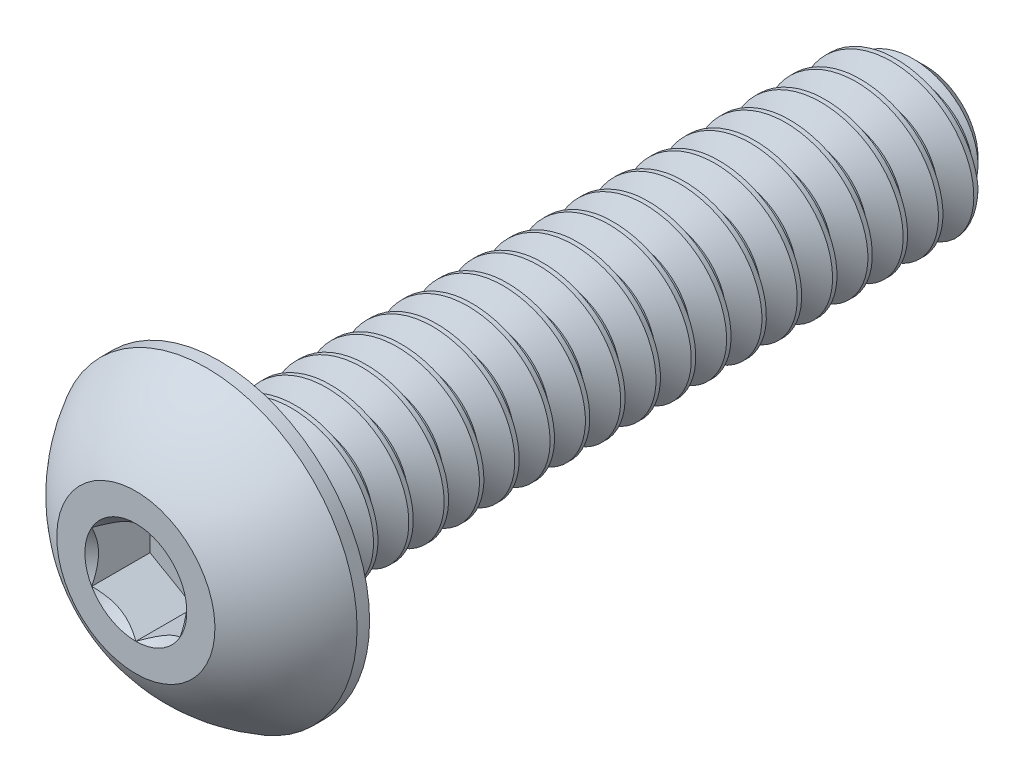
SolidWorks part; units mm, degrees
ref_plane "Front" through (0, 0, 0) normal (0, 0, 1) x (1, 0, 0)
ref_plane "Top" through (0, 0, 0) normal (0, 1, 0) x (1, 0, 0)
ref_plane "Right" through (0, 0, 0) normal (1, 0, 0) x (0, 0, -1)
sketch "Sketch1" plane through (0, 0, 0) normal (1, 0, 0) x (0, 0, -1)
  line L2 (1.4986, 1.4224) -> (14.1986, 1.4224)
  line L3 (14.1986, 1.4224) -> (14.1986, 0)
  line L4 (14.1986, 0) -> (1.4986, 0)
  line L6 (1.2738, 2.7051) -> (1.4986, 2.7051) construction
  line L7 (14.1986, 1.4224) -> (14.1986, -1.4224) construction
  line L8 (0, 0) -> (1.4986, 0) construction
  line L9 (1.4986, 2.7051) -> (1.4986, -2.7051) construction
  line L11 (1.4986, 1.4224) -> (1.4986, 0)
  line L13 (0, 0.7937) -> (0, -0.7937) construction
  line L14 (0, 0.7937) -> (0, 1.4224) construction
  arc A3 (0, 1.4224) -> (1.2738, 2.7051) centre (2.7151, 0) cw construction
  dimension "D1" = 0.2248
revolve "Revolve1" add sketch "Sketch1" angle 360 mid plane about L4
sketch "Sketch3" plane through (0, 0, -14.1986) normal (0, 0, -1) x (-1, 0, 0)
  circle A0 centre (0, 0) radius 1.4224
curve "Helix/Spiral1" pitch 0.635 height 13.335 radius 1.4224 centre (0, 0, -14.1986) axis (0, 0, 1) start towards (0, 1, 0)
sketch "Sketch2" plane through (0, 0, 0) normal (1, 0, 0) x (0, 0, -1)
  line L0 (14.1986, 1.4224) -> (14.7542, 1.4224)
  line L1 (14.7542, 1.4224) -> (14.5161, 1.01)
  line L2 (14.5161, 1.01) -> (14.4367, 1.01)
  line L3 (14.4367, 1.01) -> (14.1986, 1.4224)
  line L4 (14.3177, 1.2162) -> (14.6352, 1.2162) construction
  dimension "D1" = 60
  dimension "D2" = 0.0794
  dimension "D3" = 0.3175
chamfer "Chamfer1" distance 0.4763 angle 45 1 edges at (0, 1.4224, -14.1986)
sweep "Cut-Sweep1" cut profiles "Sketch2" path "Helix/Spiral1" align with end faces yes
sketch "Sketch7" plane through (0, 0, 0) normal (1, 0, 0) x (0, 0, -1)
  line L6 (1.2738, 2.7051) -> (1.4986, 2.7051) construction
  line L8 (0, 0) -> (1.4986, 0) construction
  line L11 (1.4986, 2.7051) -> (1.4986, -2.7051) construction
  line L12 (1.2738, 2.7051) -> (1.4986, 2.7051)
  line L13 (0, 0) -> (1.4986, 0)
  line L14 (0, 0.7937) -> (0, -0.7937) construction
  line L15 (1.4986, 2.7051) -> (1.4986, 0)
  line L16 (0, 1.4224) -> (0, 0)
  arc A2 (1.2738, 2.7051) -> (0, 1.4224) centre (2.7151, 0) ccw construction
  arc A3 (1.2738, 2.7051) -> (0, 1.4224) centre (2.7151, 0) ccw
revolve "Revolve2" add sketch "Sketch7" angle 360 mid plane about L13
sketch "Sketch5" plane through (0, 0, 0) normal (0, 0, 1) x (1, 0, 0)
  line L1 (0.7937, -0.4583) -> (0.7937, 0.4583)
  line L2 (0.7937, 0.4583) -> (0, 0.9165)
  line L3 (0, 0.9165) -> (-0.7937, 0.4583)
  line L4 (-0.7937, 0.4583) -> (-0.7937, -0.4583)
  line L5 (-0.7937, -0.4583) -> (0, -0.9165)
  line L6 (0, -0.9165) -> (0.7937, -0.4583)
  circle A0 centre (0, 0) radius 0.7937 construction
extrude "Cut-Extrude2" cut sketch "Sketch5" against normal blind 1.049
sketch "Sketch6" plane through (0, 0, 0) normal (0, 0, 1) x (1, 0, 0)
  circle A0 centre (0, 0) radius 0.9165
extrude "Cut-Extrude3" cut sketch "Sketch6" against normal blind 1.049 draft 45
sketch "Sketch9" [suppressed] plane through (0, 0, -1.4986) normal (0, 0, 1) x (1, 0, 0)
  circle A2 centre (0, 0) radius 1.4224
extrude "Boss-Extrude2" [suppressed] add sketch "Sketch9" against normal offset from surface (12.7 mm away) 31.75 up to face at (0, 0.9462, -14.1986)
sketch "Sketch10" plane through (0, 0, 0) normal (1, 0, 0) x (0, 0, -1)
  line L0 (14.1986, 1.4224) -> (14.1986, -1.4224) construction
  point P0 (13.2461, -1.4224)
  dimension "D1" = 0.9525
equation "\"D3@Helix/Spiral1\" = \"Lg@Sketch1\" + \"D4@Helix/Spiral1\""
equation "\"D2@Sketch2\" = \"D4@Helix/Spiral1\" * .125"
equation "\"D3@Sketch2\" = \"D4@Helix/Spiral1\" * .5"
equation "\"D1@Chamfer1\" = \"D4@Helix/Spiral1\" * .75"
equation "\"D1@Cut-Extrude2\" = \"Head Ht@Sketch1\" * .7"
equation "\"D1@Sketch1\" = \"Head Ht@Sketch1\" * .15"
equation "\"D1@Sketch10\" = \"D4@Helix/Spiral1\" * 1.5"
equation "\"D1@Cut-Extrude3\" = \"D1@Cut-Extrude2\""
